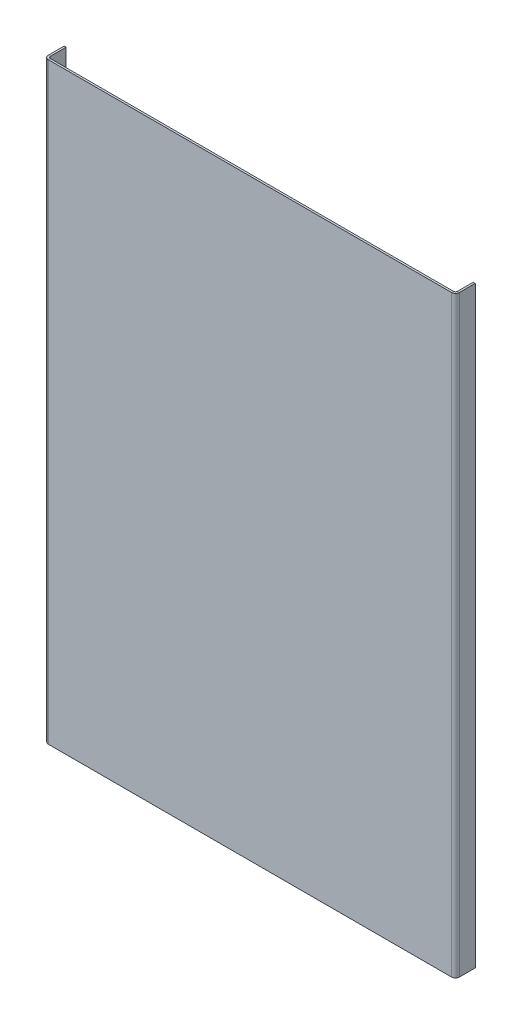
SolidWorks part; units mm, degrees
note: The reader was unsure of these and kept them because the rebuilt part matched: flange length of "Edge-Flange1".
ref_plane "Front Plane" through (0, 0, 0) normal (0, 0, 1) x (1, 0, 0)
ref_plane "Top Plane" through (0, 0, 0) normal (0, 1, 0) x (1, 0, 0)
ref_plane "Right Plane" through (0, 0, 0) normal (1, 0, 0) x (0, 0, -1)
sketch "Sketch1" plane through (0, 0, 0) normal (0, 0, 1) x (1, 0, 0)
  line L1 (-102, -150) -> (102, -150)
  line L2 (-102, -150) -> (-102, 150)
  line L3 (-102, 150) -> (102, 150)
  line L4 (102, -150) -> (102, 150)
  line L5 (-102, -150) -> (102, 150) construction
  line L6 (-102, 150) -> (102, -150) construction
  point P0 (0, 0)
  dimension "D1" = 204
  dimension "D2" = 300
base flange "Base-Flange1" sketch "Sketch1" thickness 1 reverse thickness direction no parameters "D1"=1
edge flange "Edge-Flange1" sketch "Sketch8" flange angle 90 flange length 10 flange position bend outside bend radius 1 thickness 1 relief rectangular parameters "D6"=10
sketch "Sketch8" plane through (102, 0, -1) normal (-1, 0, 0) x (0, 1, 0)
  line L1 (150, 0) -> (-150, 0) construction
  line L2 (-150, 0) -> (-150, 9)
  line L3 (-150, 9) -> (150, 9)
  line L4 (150, 9) -> (150, 0)
  line L5 (150, 0) -> (-150, 0)
bend "EdgeBend1" bend radius 1 bend angle 90 parameters "D5"=1
mirror "Mirror1" about plane through (0, 0, 0) normal (1, 0, 0) of "Edge-Flange1"
bend "MirrorBend1" bend radius 1 bend angle 90 parameters "D5"=2
sketch "Bend-Lines1" [suppressed] plane through (0, 0, 0) normal (0, 1, 0) x (1, 0, 0)
sketch "Bounding-Box1" [suppressed] plane through (0, 0, 0) normal (0, 1, 0) x (1, 0, 0)
sheet metal parameters "Sheet-Metal1" thickness 1 parameters "D1"=1
flat pattern "Flat-Pattern1" [suppressed]
sketch "Bend-Lines2" plane through (0, 0, 0) normal (0, 1, 0) x (1, 0, 0)
sketch3d "Bounding-Box2" [suppressed]
  line L0 (-100, 150, 0) -> (-100, -150, 0) construction
  line L1 (100, 150, 0) -> (100, -150, 0) construction
  line L2 (-100, 150, 0) -> (100, 150, 0) construction
  line L3 (-100, -150, 0) -> (100, -150, 0) construction
sheet metal parameters "Sheet-Metal2" thickness 1 parameters "D1"=1
flat pattern "Flat-Pattern1"
sketch "Bend-Lines2" plane through (0, 0, 0) normal (0, 0, 1) x (1, 0, 0)
  line L0 (101.1781, -150) -> (101.1781, 150) construction
  line L1 (101.1781, -150) -> (101.1781, 150) construction
sketch3d "Bounding-Box2" [suppressed]
  line L0 (110.3562, 150, 0) -> (110.3562, -150, 0) construction
  line L1 (-100, 150, 0) -> (-100, -150, 0) construction
  line L2 (110.3562, 150, 0) -> (-100, 150, 0) construction
  line L3 (110.3562, -150, 0) -> (-100, -150, 0) construction
bend of the flat pattern "Flatten-<EdgeBend1>1"
sheet metal parameters "Sheet-Metal3" thickness 1 parameters "D1"=1
flat pattern "Flat-Pattern1"
sketch "Bend-Lines2" plane through (0, 0, 0) normal (0, 0, 1) x (1, 0, 0)
  line L0 (103.1781, -150) -> (103.1781, 150) construction
  line L1 (103.1781, -150) -> (103.1781, 150) construction
  line L2 (-103.1781, 150) -> (-103.1781, -150) construction
  line L3 (-103.1781, 150) -> (-103.1781, -150) construction
sketch3d "Bounding-Box2" [suppressed]
  line L0 (112.3562, 150, 0) -> (112.3562, -150, 0) construction
  line L1 (-112.3562, 150, 0) -> (-112.3562, -150, 0) construction
  line L2 (112.3562, 150, 0) -> (-112.3562, 150, 0) construction
  line L3 (112.3562, -150, 0) -> (-112.3562, -150, 0) construction
bend of the flat pattern "Flatten-<EdgeBend1>1"
bend of the flat pattern "Flatten-<MirrorBend1>1"
